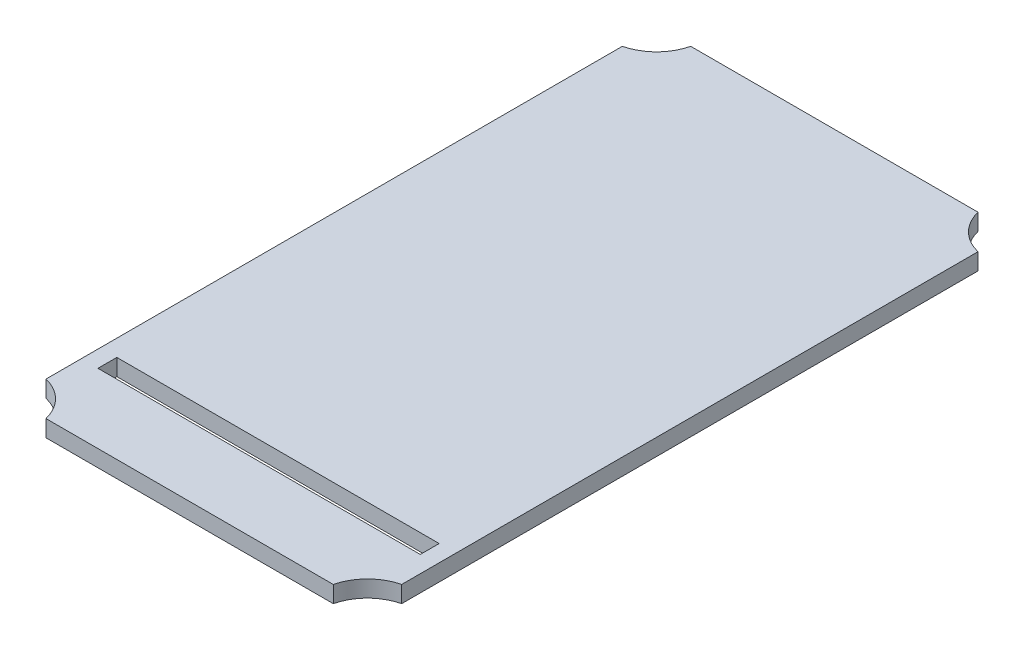
SolidWorks part; units mm, degrees
ref_plane "Front Plane" through (0, 0, 0) normal (0, 0, 1) x (1, 0, 0)
ref_plane "Top Plane" through (0, 0, 0) normal (0, 1, 0) x (1, 0, 0)
ref_plane "Right Plane" through (0, 0, 0) normal (1, 0, 0) x (0, 0, -1)
sketch "Sketch1" plane through (0, 0, 0) normal (0, 1, 0) x (1, 0, 0)
  line L1 (19, -32) -> (-19, -32)
  line L2 (19, -32) -> (19, 32)
  line L3 (19, 32) -> (-19, 32)
  line L4 (-19, -32) -> (-19, 32)
  line L5 (19, -32) -> (-19, 32) construction
  line L6 (19, 32) -> (-19, -32) construction
  line L7 (17, -30) -> (-17, -30)
  line L8 (17, -30) -> (17, 30)
  line L9 (17, 30) -> (-17, 30)
  line L10 (-17, -30) -> (-17, 30)
  line L11 (17, -30) -> (-17, 30) construction
  line L12 (17, 30) -> (-17, -30) construction
  point P0 (0, 0)
  point P6 (0, 0)
  dimension "D1" = 38
  dimension "D2" = 64
  dimension "D3" = 2
  dimension "D4" = 2
extrude "Boss-Extrude1" add sketch "Sketch1" along normal blind 1.5 contours L10 L7 L8 L9 region at (0, 0, 0)
sketch "Sketch5" plane through (0, 1.5, 0) normal (0, 1, 0) x (1, 0, 0)
  line L0 (-17, -30) -> (-17, 30) construction
  line L1 (17, 30) -> (-17, 30) construction
  line L2 (0, 30) -> (0, -30) construction
  line L3 (17, -30) -> (-17, -30) construction
  line L4 (-17, 25.8) -> (-17, 30)
  line L5 (17, -30) -> (17, 30) construction
  line L6 (17, 0) -> (-17, 0) construction
  line L7 (-17, 30) -> (-12.8, 30)
  line L8 (17, 30) -> (12.8, 30)
  line L9 (17, 25.8) -> (17, 30)
  line L10 (17, -25.8) -> (17, -30)
  line L11 (17, -30) -> (12.8, -30)
  line L12 (-17, -30) -> (-12.8, -30)
  line L13 (-17, -25.8) -> (-17, -30)
  arc A0 (-17, 25.8) -> (-12.8, 30) centre (-17, 30) ccw
  arc A1 (17, 25.8) -> (12.8, 30) centre (17, 30) cw
  arc A2 (17, -25.8) -> (12.8, -30) centre (17, -30) ccw
  arc A3 (-17, -25.8) -> (-12.8, -30) centre (-17, -30) cw
  dimension "D1" = 4.2
extrude "Cut-Extrude2" cut sketch "Sketch5" against normal blind 1.5
sketch "Sketch6" plane through (0, 1.5, 0) normal (0, 1, 0) x (1, 0, 0)
  line L0 (-17, -25.8) -> (-17, 25.8) construction
  line L1 (16, -29) -> (-16, -29)
  line L2 (16, -29) -> (16, 29)
  line L3 (16, 29) -> (-16, 29)
  line L4 (-16, -29) -> (-16, 29)
  line L5 (16, -29) -> (-16, 29) construction
  line L6 (16, 29) -> (-16, -29) construction
  line L7 (12.8, 30) -> (-12.8, 30) construction
  point P0 (0, 0)
  dimension "D1" = 1
  dimension "D2" = 1
extrude "Cut-Extrude3" cut sketch "Sketch6" against normal blind 1.5 flip side to cut
sketch "Sketch7" plane through (0, 1.5, 0) normal (0, 1, 0) x (1, 0, 0)
  line L0 (0, -29) -> (0, -15.533) construction
  line L1 (-14.5, -22.75) -> (14.5, -22.75)
  line L2 (-14.5, -22.75) -> (-14.5, -21.05)
  line L3 (-14.5, -21.05) -> (14.5, -21.05)
  line L4 (14.5, -22.75) -> (14.5, -21.05)
  line L5 (-14.5, -22.75) -> (14.5, -21.05) construction
  line L6 (-14.5, -21.05) -> (14.5, -22.75) construction
  line L7 (-12.9208, -29) -> (12.9208, -29) construction
  point P4 (0, -21.9)
  point P12 (0, 0)
  point P13 (0, 0)
  dimension "D1" = 29
  dimension "D2" = 1.7
  dimension "D3" = 6.25
extrude "Cut-Extrude4" cut sketch "Sketch7" against normal blind 10
